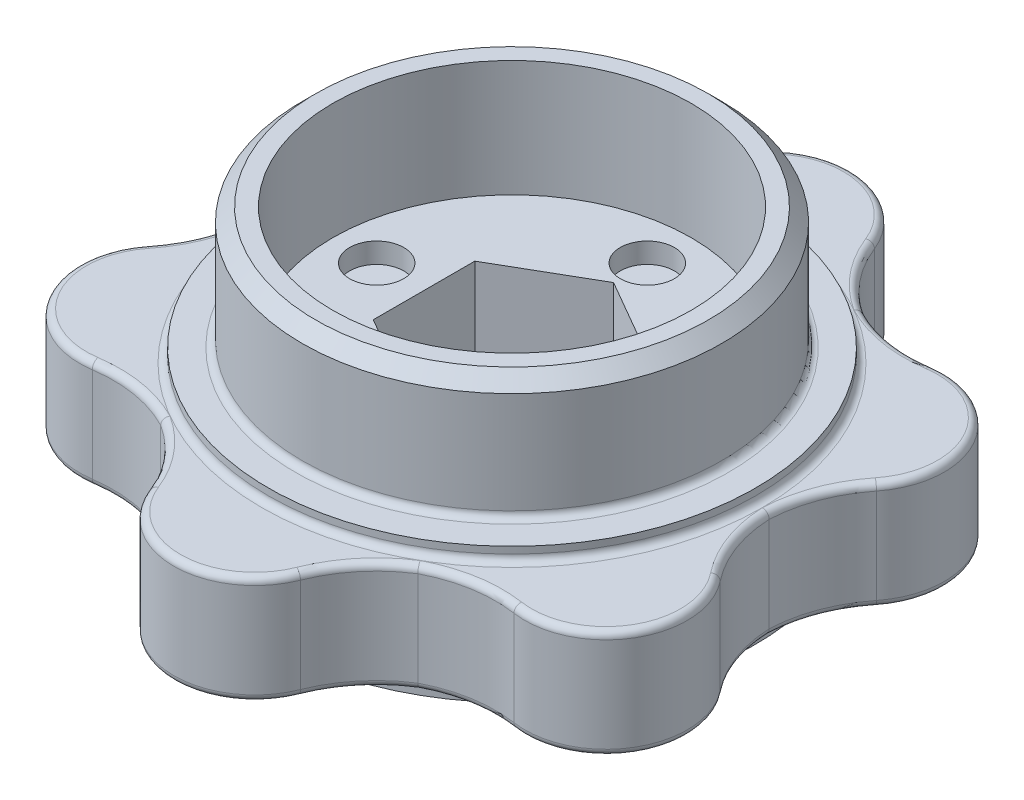
SolidWorks part; units mm, degrees
ref_plane "Front Plane" through (0, 0, 0) normal (0, 0, 1) x (1, 0, 0)
ref_plane "Top Plane" through (0, 0, 0) normal (0, 1, 0) x (1, 0, 0)
ref_plane "Right Plane" through (0, 0, 0) normal (1, 0, 0) x (0, 0, -1)
sketch "Sketch1" plane through (0, 0, 0) normal (0, 1, 0) x (1, 0, 0)
  circle A0 centre (0, 0) radius 19
  circle A1 centre (0, 19) radius 6
  circle A2 centre (16.4545, 9.5) radius 6
  circle A3 centre (16.4545, -9.5) radius 6
  circle A4 centre (0, -19) radius 6
  circle A5 centre (-16.4545, -9.5) radius 6
  circle A6 centre (-16.4545, 9.5) radius 6
  point P11 (0, 0)
  dimension "D1" = 38
  dimension "D3" = 12
  dimension "D2" = 6
extrude "Boss-Extrude1" add sketch "Sketch1" along normal blind 8 contours A6 A0 A5 A4 A3 A2 A1 | A0 A6 | A0 A6 | A0 A1 | A0 A1 | A0 A2 | A0 A2 | A0 A3 | A0 A3 | A0 A4 | A0 A4 | A0 A5 | A0 A5 | A6 region at (0, 0, 0) region at (14.1081, 0, -8.1453) region at (18.5054, 0, -10.6841) region at (18.5054, 0, 10.6841) region at (14.1081, 0, 8.1453) region at (0, 0, -16.2906) region at (0, 0, -21.3682) region at (0, 0, 21.3682) region at (0, 0, 16.2906) region at (-14.1081, 0, -8.1453) region at (-18.5054, 0, -10.6841) region at (-18.5054, 0, 10.6841) region at (-14.1081, 0, 8.1453)
fillet "Fillet2" radius 10 12 edges at (5.9247, 4, 18.0526) (12.6717, 4, 14.1573) (18.5964, 4, 3.8953) (18.5964, 4, -3.8953) (12.6717, 4, -14.1573) (5.9247, 4, -18.0526) (-5.9247, 4, -18.0526) (-12.6717, 4, -14.1573) (-18.5964, 4, -3.8953) (-18.5964, 4, 3.8953) (-5.9247, 4, 18.0526) (-12.6717, 4, 14.1573)
ref_plane "Plane1" through (0, 4, 0) normal (0, -1, 0) x (-1, 0, 0)
sketch "Sketch2" plane through (0, 4, 0) normal (0, -1, 0) x (-1, 0, 0)
  circle A0 centre (0, 0) radius 18
  dimension "D1" = 36
extrude "Boss-Extrude2" add sketch "Sketch2" along normal blind 5 and the other way blind 5
sketch "Sketch3" plane through (0, 4, 0) normal (0, -1, 0) x (-1, 0, 0)
  circle A0 centre (0, 0) radius 15.5
  dimension "D1" = 31
extrude "Boss-Extrude3" add sketch "Sketch3" along normal blind 5.5 and the other way blind 14
sketch "Sketch4" plane through (0, 4, 0) normal (0, -1, 0) x (-1, 0, 0)
  line L1 (0, 7.5056) -> (-6.5, 3.7528)
  line L2 (-6.5, 3.7528) -> (-6.5, -3.7528)
  line L3 (-6.5, -3.7528) -> (0, -7.5056)
  line L4 (0, -7.5056) -> (6.5, -3.7528)
  line L5 (6.5, -3.7528) -> (6.5, 3.7528)
  line L6 (6.5, 3.7528) -> (0, 7.5056)
  circle A0 centre (0, 0) radius 6.5 construction
  dimension "D1" = 13
extrude "Cut-Extrude1" cut sketch "Sketch4" against normal through all and the other way blind 1
sketch "Sketch5" plane through (0, 3, 0) normal (0, 1, 0) x (1, 0, 0)
  circle A0 centre (0, 0) radius 4.5
  dimension "D1" = 9
extrude "Cut-Extrude2" cut sketch "Sketch5" against normal through all
sketch "Sketch6" plane through (0, -1.5, 0) normal (0, -1, 0) x (1, 0, 0)
  circle A0 centre (0, 0) radius 13.25
  dimension "D1" = 26.5
extrude "Cut-Extrude3" cut sketch "Sketch6" against normal blind 3
ref_plane "Plane2" through (0, 9.4, 0) normal (0, 1, 0) x (1, 0, 0)
sketch "Sketch9" plane through (0, 9.4, 0) normal (0, 1, 0) x (1, 0, 0)
  circle A0 centre (0, 0) radius 13.25
  dimension "D1" = 26.5
extrude "Cut-Extrude5" cut sketch "Sketch9" along normal through all
sketch "Sketch10" plane through (0, 9.4, 0) normal (0, 1, 0) x (1, 0, 0)
  circle A0 centre (0, 0) radius 10 construction
  circle A1 centre (0, 10) radius 2
  circle A2 centre (0, -10) radius 2
  circle A3 centre (-10, 0) radius 2
  circle A4 centre (10, 0) radius 2
  dimension "D1" = 4
  dimension "D2" = 20
extrude "Cut-Extrude6" cut sketch "Sketch10" against normal blind 1.5
chamfer "Chamfer1" distance 1 angle 45 1 edges at (0, 18, -15.5)
fillet "Fillet4" radius 0.5 18 edges at (12.4606, 8, 15.4681) (19.6261, 8, 3.0572) (21.6506, 8, 12.5) (0, 8, -25) (7.1655, 8, -18.5253) (12.4606, 8, -15.4681) (21.6506, 8, -12.5) (19.6261, 8, -3.0572) (7.1655, 8, 18.5253) (0, 8, 25) (-7.1655, 8, 18.5253) (-12.4606, 8, 15.4681) (-21.6506, 8, 12.5) (-19.6261, 8, 3.0572) (-19.6261, 8, -3.0572) (-21.6506, 8, -12.5) (-12.4606, 8, -15.4681) (-7.1655, 8, -18.5253)
fillet "Fillet5" radius 0.5 19 edges at (-12.4606, 0, 15.4681) (-7.1655, 0, 18.5253) (0, 0, 25) (7.1655, 0, 18.5253) (12.4606, 0, 15.4681) (21.6506, 0, 12.5) (19.6261, 0, 3.0572) (19.6261, 0, -3.0572) (21.6506, 0, -12.5) (12.4606, 0, -15.4681) (7.1655, 0, -18.5253) (0, 0, -25) (-7.1655, 0, -18.5253) (-12.4606, 0, -15.4681) (-21.6506, 0, -12.5) (-19.6261, 0, -3.0572) (-19.6261, 0, 3.0572) (-21.6506, 0, 12.5) (0, 0, 18)
fillet "Fillet6" radius 0.5 2 edges at (0, 8, 18) (0, 9, -15.5)
equation "\"D2@Cut-Extrude1\"=1"
